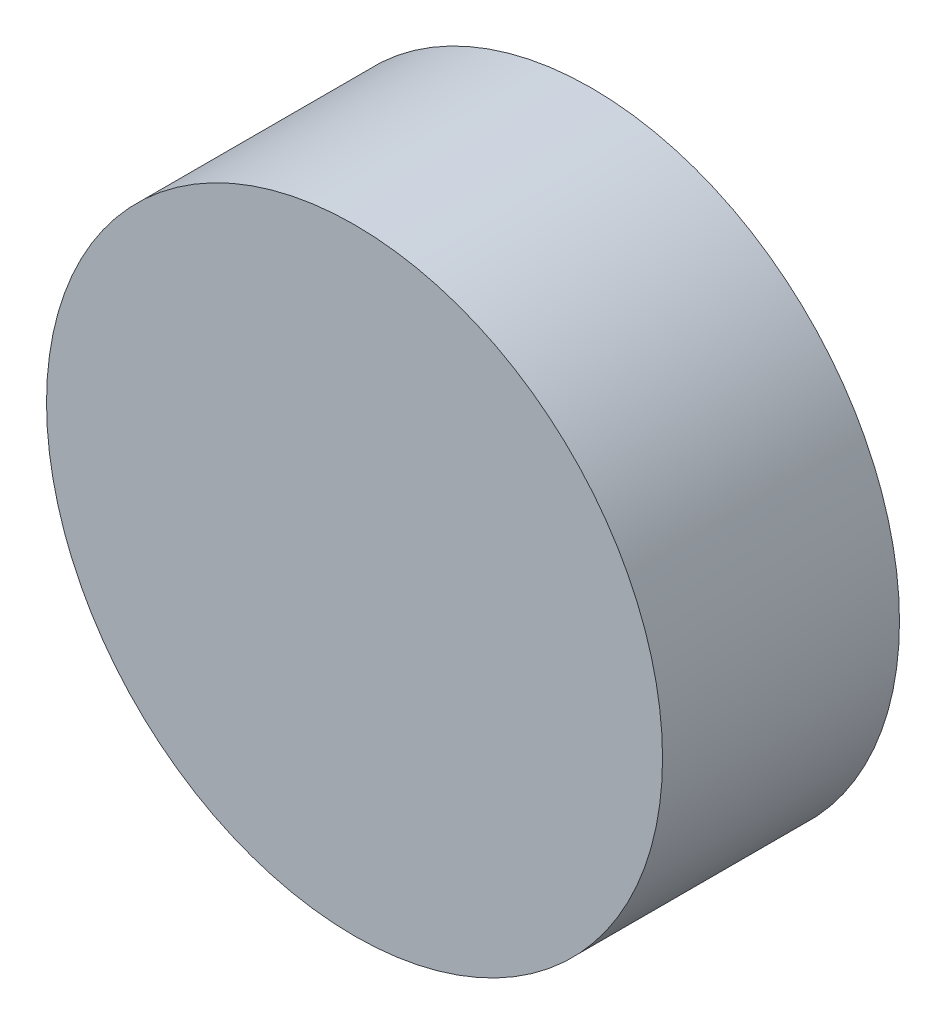
SolidWorks part; units mm, degrees
ref_plane "Спереди" through (0, 0, 0) normal (0, 0, 1) x (1, 0, 0)
ref_plane "Сверху" through (0, 0, 0) normal (0, 1, 0) x (1, 0, 0)
ref_plane "Справа" through (0, 0, 0) normal (1, 0, 0) x (0, 0, -1)
sketch "Эскиз1" plane through (0, 0, 0) normal (0, 0, 1) x (1, 0, 0)
  circle A0 centre (0, 0) radius 32.5
extrude "abot_left_wheel" add sketch "Эскиз1" along normal blind 25
ref_axis "AXIS_LEFT_WHEEL" through (0, 0, 25) along (0, 0, -1)
